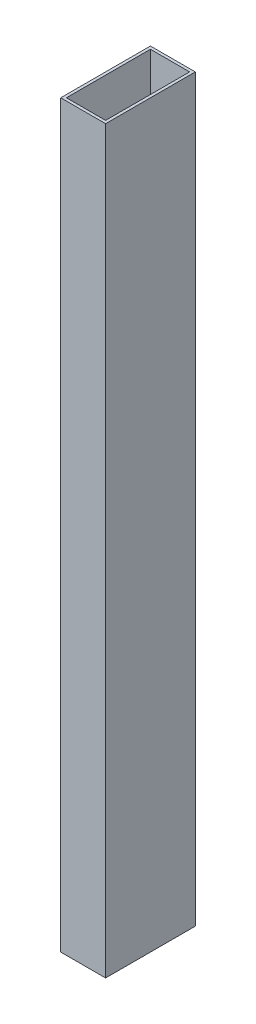
SolidWorks part; units mm, degrees
material "6061-T6 (SS)"
ref_plane "Front" through (0, 0, 0) normal (0, 0, 1) x (1, 0, 0)
ref_plane "Top" through (0, 0, 0) normal (0, 1, 0) x (1, 0, 0)
ref_plane "Right" through (0, 0, 0) normal (1, 0, 0) x (0, 0, -1)
sketch "Sketch1" plane through (0, 0, 0) normal (0, 1, 0) x (1, 0, 0)
  line L1 (12.7, 25.4) -> (-12.7, 25.4)
  line L2 (12.7, 25.4) -> (12.7, -25.4)
  line L3 (12.7, -25.4) -> (-12.7, -25.4)
  line L4 (-12.7, 25.4) -> (-12.7, -25.4)
  line L5 (12.7, 25.4) -> (-12.7, -25.4) construction
  line L6 (12.7, -25.4) -> (-12.7, 25.4) construction
  point P0 (0, 0)
  dimension "D1" = 25.4
  dimension "D2" = 50.8
extrude "Extrude-Thin1" add sketch "Sketch1" along normal up to surface (419.1 mm away) thin thin type one direction reverse wall 1.5875
